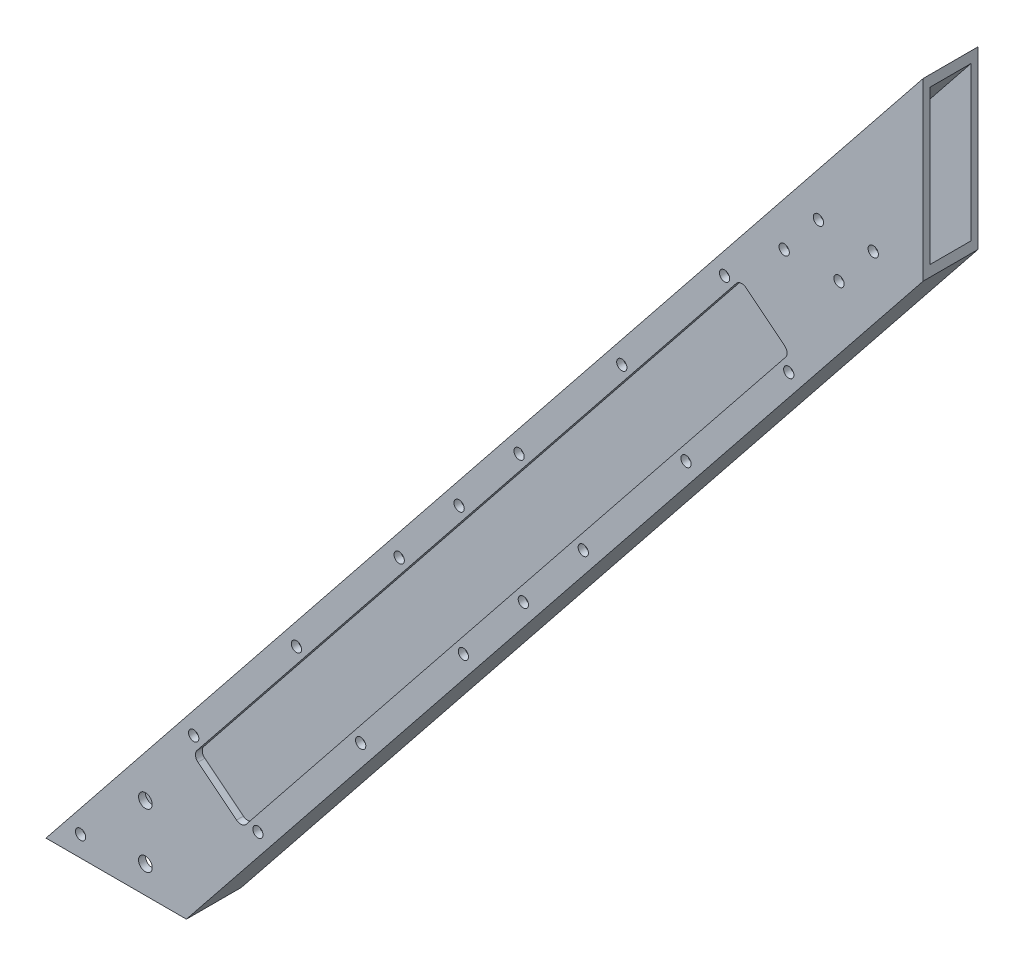
SolidWorks part; units mm, degrees
material "6063-T1"
ref_plane "Front Plane" through (0, 0, 0) normal (0, 0, 1) x (1, 0, 0)
ref_plane "Top Plane" through (0, 0, 0) normal (0, 1, 0) x (1, 0, 0)
ref_plane "Right Plane" through (0, 0, 0) normal (1, 0, 0) x (0, 0, -1)
sketch "Sketch1" plane through (0, 0, 0) normal (0, 0, 1) x (1, 0, 0)
  line L0 (0, 0) -> (406.4, 508)
  line L1 (406.4, 508) -> (406.4, 426.6803)
  line L2 (406.4, 426.6803) -> (65.0557, 0)
  line L3 (65.0557, 0) -> (0, 0)
  dimension "D1" = 406.4
  dimension "D2" = 508
  dimension "D3" = 50.8
extrude "Boss-Extrude1" add sketch "Sketch1" along normal blind 25.4
shell "Shell1" thickness 3.175 removed face at (406.4, 467.3402, 12.7) removed face at (32.5279, 0, 12.7)
sketch "Sketch2" plane through (0, 0, 25.4) normal (0, 0, 1) x (1, 0, 0)
  line L0 (90.7409, 49.3868) -> (344.6169, 366.7319)
  line L1 (90.7409, 49.3868) -> (67.9317, 67.6342)
  line L2 (344.6169, 366.7319) -> (321.8077, 384.9793)
  line L3 (67.9317, 67.6342) -> (321.8077, 384.9793)
  line L4 (406.4, 508) -> (0, 0) construction
  line L5 (65.0557, 0) -> (406.4, 426.6803) construction
  line L6 (79.3363, 58.5105) -> (333.2123, 375.8556) construction
  line L7 (194.8697, 226.3067) -> (217.6789, 208.0594) construction
  line L8 (186.4402, 233.0503) -> (226.1084, 201.3158) construction
  circle A0 centre (68.4275, 75.3695) radius 2.3813
  circle A1 centre (116.0293, 134.8717) radius 2.3813
  circle A2 centre (163.6311, 194.3739) radius 2.3812
  circle A3 centre (193.3822, 170.573) radius 2.3812
  circle A4 centre (145.7804, 111.0708) radius 2.3813
  circle A5 centre (98.1786, 51.5686) radius 2.3813
  circle A6 centre (344.1211, 358.9966) radius 2.3813
  circle A7 centre (296.5193, 299.4944) radius 2.3813
  circle A8 centre (248.9176, 239.9922) radius 2.3812
  circle A9 centre (219.1664, 263.7931) radius 2.3812
  circle A10 centre (266.7682, 323.2953) radius 2.3813
  circle A11 centre (314.37, 382.7975) radius 2.3813
  circle A12 centre (191.3988, 229.0835) radius 2.3813
  circle A13 centre (221.1499, 205.2826) radius 2.3813
  dimension "D5" = 4.7625
  dimension "D9" = 4.7625
  dimension "D10" = 4.7625
  dimension "D1" = 406.4
  dimension "D2" = 29.21
  dimension "D3" = 10.795
  dimension "D4" = 57.15
  dimension "D6" = 6.35
  dimension "D7" = 6.35
  dimension "D11" = 6.35
  dimension "D12" = 6.35
  dimension "D8" = 3
extrude "Cut-Extrude1" cut sketch "Sketch2" against normal blind 5.08
fillet "Fillet1" radius 3.175 4 edges at (321.8077, 384.9793, 23.8125) (344.6169, 366.7319, 23.8125) (90.7409, 49.3868, 23.8125) (67.9317, 67.6342, 23.8125)
sketch "Sketch3" plane through (0, 0, 25.4) normal (0, 0, 1) x (1, 0, 0)
  line L1 (0, 0) -> (65.0557, 0) construction
  line L2 (406.4, 508) -> (0, 0) construction
  circle A0 centre (46.0481, 12.7) radius 3.175
  circle A1 centre (16.002, 9.525) radius 2.3813
  circle A2 centre (46.0481, 38.1) radius 3.175
  circle A3 centre (341.9935, 407.162) radius 2.3813
  circle A4 centre (357.8608, 426.9961) radius 2.3813
  circle A5 centre (367.3935, 407.162) radius 2.3813
  circle A6 centre (383.2608, 426.9961) radius 2.3813
  point P22 (0, 0)
  point P23 (0, 0)
  point P24 (382.7027, 425.3541)
  point P25 (0, 0)
  dimension "D1" = 6.35
  dimension "D5" = 4.7625
  dimension "D7" = 6.35
  dimension "D15" = 4.7625
  dimension "D16" = 4.7625
  dimension "D17" = 4.7625
  dimension "D18" = 4.7625
  dimension "D2" = 12.7
  dimension "D3" = 22.86
  dimension "D4" = 9.525
  dimension "D6" = 16.002
  dimension "D8" = 25.4
  dimension "D9" = 12.7
  dimension "D10" = 100.838
  dimension "D11" = 25.4
  dimension "D12" = 12.7
  dimension "D13" = 25.4
  dimension "D14" = 25.4
extrude "Cut-Extrude2" cut sketch "Sketch3" against normal through all
